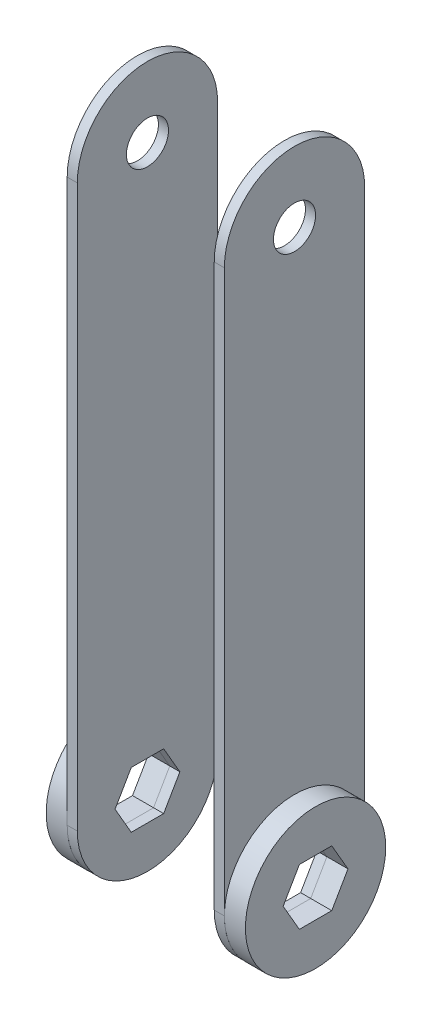
SolidWorks part; units mm, degrees
material "Commercially Pure CP-Ti UNS R50700  Grade 4 (SS)"
ref_plane "Front Plane" through (0, 0, 0) normal (0, 0, 1) x (1, 0, 0)
ref_plane "Top Plane" through (0, 0, 0) normal (0, 1, 0) x (1, 0, 0)
ref_plane "Right Plane" through (0, 0, 0) normal (1, 0, 0) x (0, 0, -1)
sketch "Sketch2" plane through (0, 0, 0) normal (0, 0, 1) x (1, 0, 0)
  line L0 (-27.352, 0) -> (25.4498, 0) construction
  line L1 (-15.494, -15.875) -> (-17.78, -15.875)
  line L2 (-15.494, -15.875) -> (-15.494, 142.875)
  line L3 (-15.494, 142.875) -> (-17.78, 142.875)
  line L4 (-17.78, -15.875) -> (-17.78, 142.875)
  line L5 (-15.494, -15.875) -> (-17.78, 142.875) construction
  line L6 (-15.494, 142.875) -> (-17.78, -15.875) construction
  line L7 (-40.1956, 127) -> (35.7961, 127) construction
  line L8 (0, 0) -> (0, 127) construction
  line L9 (-22.5425, 15.875) -> (-17.78, 15.875)
  line L10 (-22.5425, 15.875) -> (-22.5425, -15.875)
  line L11 (-22.5425, -15.875) -> (-17.78, -15.875)
  line L12 (-17.78, 15.875) -> (-17.78, -15.875)
  line L13 (-22.5425, 15.875) -> (-17.78, -15.875) construction
  line L14 (-22.5425, -15.875) -> (-17.78, 15.875) construction
  line L15 (15.494, 142.875) -> (17.78, 142.875)
  line L16 (17.78, -15.875) -> (17.78, 142.875)
  line L17 (15.494, -15.875) -> (17.78, -15.875)
  line L18 (15.494, -15.875) -> (15.494, 142.875)
  line L19 (22.5425, -15.875) -> (17.78, -15.875)
  line L20 (17.78, 15.875) -> (17.78, -15.875)
  line L21 (22.5425, 15.875) -> (17.78, 15.875)
  line L22 (22.5425, 15.875) -> (22.5425, -15.875)
  point P4 (-16.637, 63.5)
  point P11 (-20.1612, 0)
  dimension "D1" = 2.286
  dimension "D2" = 17.78
  dimension "D3" = 127
  dimension "D4" = 15.875
  dimension "D5" = 15.875
  dimension "D6" = 4.7625
sketch "Sketch1" plane through (0, 0, 0) normal (1, 0, 0) x (0, 0, -1)
  line L0 (0, 0) -> (0, 127) construction
  line L1 (-15.875, 0) -> (-15.875, 127)
  line L2 (15.875, 0) -> (15.875, 127)
  line L3 (0, -200000) -> (0, 200127) construction
  arc A0 (-15.875, 0) -> (15.875, 0) centre (0, 0) ccw
  arc A1 (15.875, 127) -> (-15.875, 127) centre (0, 127) ccw
  circle A2 centre (0, 127) radius 4.7625
  point P3 (0, 63.5)
  point P10 (0, 131.6786)
  dimension "D3" = 9.525
  dimension "D2" = 31.75
extrude "Boss-Extrude1" add sketch "Sketch1" against normal up to vertex (-15.494 mm away) from vertex up to point (15.494, -15.875, 0) starting at point (17.78, -15.875, 0)
sketch "Sketch3" plane through (17.78, 0, 0) normal (1, 0, 0) x (0, 0, -1)
  line L0 (0, -15.875) -> (0, 15.875) construction
  circle A0 centre (0, 0) radius 15.875
extrude "Boss-Extrude2" add sketch "Sketch3" along normal up to vertex (4.7625 mm away) separate body up to point (22.5425, -15.875, 0)
sketch "Sketch4" plane through (22.5425, 0, 0) normal (1, 0, 0) x (0, 0, -1)
  line L0 (0, -15.875) -> (0, 15.875) construction
  line L1 (3.6662, -6.35) -> (7.3323, 0)
  line L2 (7.3323, 0) -> (3.6662, 6.35)
  line L3 (3.6662, 6.35) -> (-3.6662, 6.35)
  line L4 (-3.6662, 6.35) -> (-7.3323, 0)
  line L5 (-7.3323, 0) -> (-3.6662, -6.35)
  line L6 (-3.6662, -6.35) -> (3.6662, -6.35)
  circle A0 centre (0, 0) radius 6.35 construction
  dimension "D1" = 12.7
extrude "Cut-Extrude1" cut sketch "Sketch4" against normal through all
mirror "Mirror3" about plane through (0, 0, 0) normal (1, 0, 0) of bodies 104 105 101
